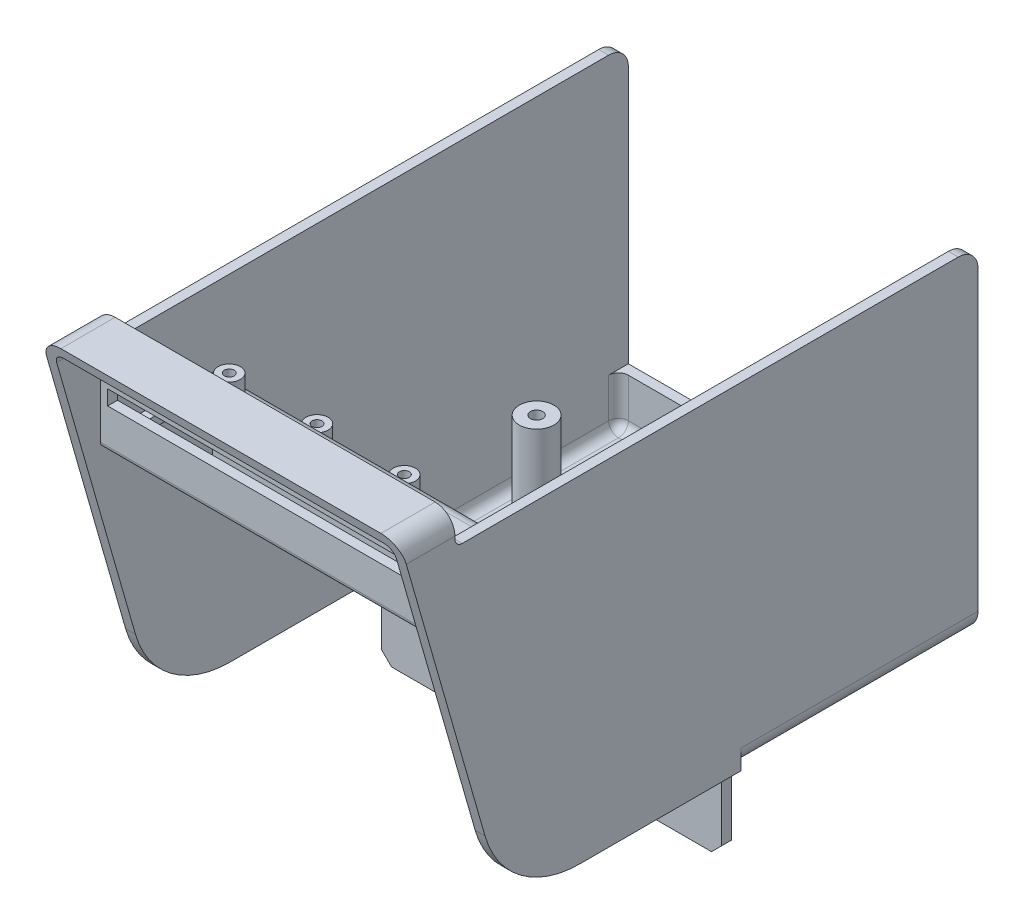
SolidWorks part; units mm, degrees
ref_plane "Front Plane" through (0, 0, 0) normal (0, 0, 1) x (1, 0, 0)
ref_plane "Top Plane" through (0, 0, 0) normal (0, 1, 0) x (1, 0, 0)
ref_plane "Right Plane" through (0, 0, 0) normal (1, 0, 0) x (0, 0, -1)
sketch "Sketch1" plane through (0, 0, 0) normal (0, 1, 0) x (1, 0, 0)
  line L1 (-36.425, -54.49) -> (36.425, -54.49)
  line L2 (-36.425, -54.49) -> (-36.425, 54.49)
  line L3 (-36.425, 54.49) -> (36.425, 54.49)
  line L4 (36.425, -54.49) -> (36.425, 54.49)
  line L5 (-36.425, -54.49) -> (36.425, 54.49) construction
  line L6 (-36.425, 54.49) -> (36.425, -54.49) construction
  point P0 (0, 0)
  dimension "D1" = 72.85
  dimension "D2" = 108.98
extrude "Boss-Extrude1" add sketch "Sketch1" along normal blind 66.66 and the other way blind 7.5
sketch "Sketch2" plane through (36.425, 0, 0) normal (1, 0, 0) x (0, 0, -1)
  line L0 (-54.49, 66.66) -> (-54.49, 43.24)
  line L1 (-54.49, 66.66) -> (-54.49, -7.5) construction
  line L2 (-54.49, 43.24) -> (-31.71, 43.24)
  line L3 (-31.71, 43.24) -> (-31.71, 25.46)
  line L4 (-31.71, 25.46) -> (-14.01, 25.46)
  line L5 (-14.01, 25.46) -> (-14.01, 7.68)
  line L6 (-14.01, 7.68) -> (2.51, 7.68)
  line L7 (2.51, 7.68) -> (2.51, -7.5)
  line L8 (-54.49, -7.5) -> (54.49, -7.5) construction
  line L9 (54.49, 66.66) -> (54.49, -7.5) construction
  line L10 (-54.49, 66.66) -> (54.49, 66.66) construction
  dimension "D1" = 23.42
  dimension "D2" = 86.2
  dimension "D3" = 41.2
  dimension "D4" = 58.98
  dimension "D5" = 68.5
  dimension "D6" = 51.98
extrude "Cut-Extrude1" cut sketch "Sketch2" against normal through all and the other way through all flip side to cut
fillet "Fillet1" radius 1 6 edges at (0, 7.68, -2.51) (0, 25.46, 14.01) (0, 43.24, 31.71) (0, 43.24, 54.49) (0, 25.46, 31.71) (0, 7.68, 14.01)
shell "Shell1" thickness 2 removed face at (0, 29.58, -54.49) removed face at (0, 66.66, 0)
sketch "Sketch3" plane through (0, 43.24, 0) normal (0, -1, 0) x (1, 0, 0)
  line L0 (-36.425, 54.49) -> (36.425, 54.49) construction
  line L1 (-32.5, 47.39) -> (32.5, 47.39)
  line L2 (-32.5, 47.39) -> (-32.5, 37.39)
  line L3 (-32.5, 37.39) -> (32.5, 37.39)
  line L4 (32.5, 47.39) -> (32.5, 37.39)
  line L5 (0, 0) -> (0, 59.3951) construction
  dimension "D1" = 65
  dimension "D2" = 10
  dimension "D3" = 7.1
extrude "Cut-Extrude2" cut sketch "Sketch3" against normal up to next
sketch "Sketch4" plane through (0, 25.46, 0) normal (0, -1, 0) x (1, 0, 0)
  line L0 (-32.5, 47.39) -> (-32.5, 37.39) construction
  line L1 (-32.5, 29.61) -> (32.5, 29.61)
  line L2 (-32.5, 29.61) -> (-32.5, 19.61)
  line L3 (-32.5, 19.61) -> (32.5, 19.61)
  line L4 (32.5, 29.61) -> (32.5, 19.61)
  line L5 (32.5, 37.39) -> (32.5, 47.39) construction
  line L6 (36.425, 31.71) -> (-36.425, 31.71) construction
  dimension "D1" = 2.1
  dimension "D2" = 10
extrude "Cut-Extrude3" cut sketch "Sketch4" against normal up to next
sketch "Sketch5" plane through (0, 7.68, 0) normal (0, -1, 0) x (1, 0, 0)
  line L0 (-32.5, 29.61) -> (-32.5, 19.61) construction
  line L1 (-32.5, 11.91) -> (32.5, 11.91)
  line L2 (-32.5, 11.91) -> (-32.5, 1.91)
  line L3 (-32.5, 1.91) -> (32.5, 1.91)
  line L4 (32.5, 11.91) -> (32.5, 1.91)
  line L5 (32.5, 19.61) -> (32.5, 29.61) construction
  line L6 (36.425, 14.01) -> (-36.425, 14.01) construction
  dimension "D1" = 10
  dimension "D2" = 2.1
extrude "Cut-Extrude4" cut sketch "Sketch5" against normal up to next
sketch "Sketch7" plane through (0, 45.24, 0) normal (0, 1, 0) x (1, 0, 0)
  line L0 (-32.5, -37.39) -> (32.5, -37.39) construction
  circle A0 centre (-28, -34.79) radius 2.25
  circle A1 centre (28, -34.79) radius 2.25
  dimension "D1" = 4.5
  dimension "D4" = 28
  dimension "D5" = 4.5
  dimension "D2" = 28
  dimension "D3" = 2.6
extrude "Boss-Extrude2" add sketch "Sketch7" along normal blind 4.5 and the other way up to next (2 mm away)
sketch "Sketch8" plane through (0, 27.46, 0) normal (0, 1, 0) x (1, 0, 0)
  line L0 (-32.5, -19.61) -> (32.5, -19.61) construction
  circle A0 centre (-28, -17.01) radius 2.25
  circle A1 centre (28, -17.01) radius 2.25
  dimension "D1" = 28
  dimension "D4" = 4.5
  dimension "D2" = 28
  dimension "D3" = 2.6
extrude "Boss-Extrude3" add sketch "Sketch8" along normal blind 4.5 and the other way up to next (2 mm away)
sketch "Sketch9" plane through (0, 9.68, 0) normal (0, 1, 0) x (1, 0, 0)
  line L0 (-32.5, -1.91) -> (32.5, -1.91) construction
  circle A0 centre (-28, 0.69) radius 2.25
  circle A1 centre (28, 0.69) radius 2.25
  dimension "D1" = 4.5
  dimension "D3" = 28
  dimension "D5" = 4.5
  dimension "D2" = 2.6
  dimension "D4" = 28
extrude "Boss-Extrude4" add sketch "Sketch9" along normal blind 4.5 and the other way up to next
sketch "Sketch10" plane through (0, 0, 54.49) normal (0, 0, 1) x (1, 0, 0)
  line L1 (-32.936, 54.3583) -> (33.0803, 54.3583)
  line L2 (-32.936, 54.3583) -> (-32.936, 51.34)
  line L3 (-32.936, 51.34) -> (33.0803, 51.34)
  line L4 (33.0803, 54.3583) -> (33.0803, 51.34)
extrude "Cut-Extrude5" cut sketch "Sketch10" against normal up to next
sketch "Sketch11" plane through (0, -5.5, 0) normal (0, 1, 0) x (1, 0, 0)
  line L0 (34.425, 54.49) -> (-34.425, 54.49) construction
  line L1 (0, 0) -> (0, 57.5418) construction
  circle A0 centre (-25, 24.49) radius 3.5
  circle A1 centre (25, 24.49) radius 3.5
  dimension "D1" = 7
  dimension "D2" = 7
  dimension "D3" = 30
  dimension "D4" = 50
extrude "Boss-Extrude5" add sketch "Sketch11" along normal blind 19.72
sketch "Sketch12" plane through (-36.425, 0, 0) normal (-1, 0, 0) x (0, 0, 1)
  line L0 (54.49, 66.66) -> (64.49, 66.66)
  line L1 (-54.49, -7.5) -> (-2.51, -7.5) construction
  line L2 (64.49, 66.66) -> (47.3791, 6.9873)
  line L4 (-54.49, -7.5) -> (28.1539, -7.5)
  line L5 (-54.49, -7.5) -> (54.49, 66.66)
  arc A1 (47.3791, 6.9873) -> (28.1539, -7.5) centre (28.1539, 12.5) cw
  dimension "D2" = 20
  dimension "D1" = 10
  dimension "D5" = 74
extrude "Boss-Extrude6" add sketch "Sketch12" against normal blind 2
mirror "Mirror1" about plane through (0, 0, 0) normal (1, 0, 0) of "Boss-Extrude6"
sketch "Sketch20" plane through (0, 66.66, 0) normal (0, 1, 0) x (1, 0, 0)
  line L1 (-34.425, -64.49) -> (34.425, -64.49)
  line L2 (-34.425, -64.49) -> (-34.425, -54.49)
  line L3 (-34.425, -54.49) -> (34.425, -54.49)
  line L4 (34.425, -64.49) -> (34.425, -54.49)
extrude "Boss-Extrude7" add sketch "Sketch20" against normal blind 2
sketch "Sketch21" plane through (36.425, 0, 0) normal (1, 0, 0) x (0, 0, -1)
  line L0 (-64.49, 66.66) -> (-63.7125, 63.9486)
  line L1 (-47.3791, 6.9873) -> (-64.49, 66.66) construction
  line L2 (-63.7125, 63.9486) -> (-66.4372, 63.9486)
  line L3 (-66.4372, 63.9486) -> (-64.49, 66.66)
extrude "Cut-Extrude12" cut sketch "Sketch21" against normal through all
chamfer "Chamfer1" [suppressed] distance 4 angle 15
fillet "Fillet3" [suppressed] radius 1
sketch "Sketch13" plane through (0, -7.5, 0) normal (0, -1, 0) x (1, 0, 0)
  line L1 (-34.425, -54.49) -> (34.425, -54.49)
  line L2 (-34.425, -54.49) -> (-34.425, -51.99)
  line L3 (-34.425, -51.99) -> (34.425, -51.99)
  line L4 (34.425, -54.49) -> (34.425, -51.99)
  dimension "D1" = 2.5
extrude "Cut-Extrude6" cut sketch "Sketch13" against normal up to next
fillet "Fillet4" radius 3 2 edges at (-35.425, 66.66, -54.49) (35.425, 66.66, -54.49)
sketch "Sketch14" plane through (0, 66.66, 0) normal (0, 1, 0) x (1, 0, 0)
  line L11 (-35.425, 64.9406) -> (35.425, 64.9406)
  line L15 (-35.425, -32.71) -> (-35.425, -53.49)
  line L17 (-35.425, -53.49) -> (35.425, -53.49)
  line L18 (35.425, -53.49) -> (35.425, 51.49)
  line L19 (-35.425, 64.9406) -> (-35.425, -53.49)
  line L20 (-35.425, -53.49) -> (35.425, -53.49)
  line L21 (35.425, -53.49) -> (35.425, 64.9406)
  dimension "D1" = 1
extrude "Cut-Extrude7" cut sketch "Sketch14" against normal blind 1.5
sketch "Sketch16" plane through (0, -7.5, 0) normal (0, -1, 0) x (1, 0, 0)
  line L0 (34.425, -51.99) -> (-34.425, -51.99) construction
  circle A0 centre (-25, -24.49) radius 1.25
  circle A1 centre (25, -24.49) radius 1.25
  dimension "D1" = 2.5
  dimension "D2" = 2.5
  dimension "D3" = 27.5
  dimension "D4" = 27.5
extrude "Cut-Extrude8" cut sketch "Sketch16" against normal up to next
sketch "Sketch17" plane through (0, 14.18, 0) normal (0, 1, 0) x (1, 0, 0)
  circle A0 centre (-28, 0.69) radius 1
  circle A1 centre (28, 0.69) radius 1
  dimension "D1" = 2
  dimension "D2" = 2
extrude "Cut-Extrude9" cut sketch "Sketch17" against normal blind 4
sketch "Sketch18" plane through (0, 31.96, 0) normal (0, 1, 0) x (1, 0, 0)
  circle A0 centre (-28, -17.01) radius 1
  circle A1 centre (28, -17.01) radius 1
  dimension "D1" = 2
  dimension "D2" = 2
extrude "Cut-Extrude10" cut sketch "Sketch18" against normal blind 4
sketch "Sketch19" plane through (0, 49.74, 0) normal (0, 1, 0) x (1, 0, 0)
  circle A0 centre (-28, -34.79) radius 1
  circle A1 centre (28, -34.79) radius 1
  dimension "D1" = 2
  dimension "D2" = 2
extrude "Cut-Extrude11" cut sketch "Sketch19" against normal blind 4
sketch "Sketch22" plane through (36.425, 0, 0) normal (1, 0, 0) x (0, 0, -1)
  line L0 (54.49, 63.66) -> (54.49, -7.5) construction
  line L1 (54.49, 60.66) -> (-53.49, 60.66)
  line L2 (54.49, 60.66) -> (54.49, 66.66)
  line L3 (54.49, 66.66) -> (-53.49, 66.66)
  line L4 (-53.49, 60.66) -> (-53.49, 66.66)
  line L5 (48.51, 60.66) -> (-51.99, 60.66) construction
extrude "Cut-Extrude13" cut sketch "Sketch22" against normal through all
sketch "Sketch23" plane through (0, 60.66, 0) normal (0, 1, 0) x (1, 0, 0)
  line L1 (-34.425, -52.49) -> (34.425, -52.49)
  line L2 (-34.425, -52.49) -> (-34.425, -53.49)
  line L3 (-34.425, -53.49) -> (34.425, -53.49)
  line L4 (34.425, -52.49) -> (34.425, -53.49)
  line L5 (34.425, -52.49) -> (34.425, -32.71) construction
  line L6 (-36.425, -53.49) -> (36.425, -53.49) construction
extrude "Boss-Extrude8" add sketch "Sketch23" along normal offset from surface (4 mm away) 2 up to face at (0, 66.66, 58.99)
fillet "Fillet6" radius 2 2 edges at (-34.425, 64.66, 52.99) (34.425, 64.66, 52.99)
fillet "Fillet7" radius 2 2 edges at (34.425, 64.66, 59.2033) (-34.425, 64.66, 59.2033)
fillet "Fillet8" radius 4 2 edges at (36.425, 66.66, 58.99) (-36.425, 66.66, 58.99)
sketch "Sketch28" plane through (0, -7.5, 0) normal (0, -1, 0) x (1, 0, 0)
  line L0 (34.425, -2.51) -> (34.425, 28.1539) construction
  line L1 (-34.425, -2.51) -> (34.425, -2.51)
  line L2 (-34.425, -2.51) -> (-34.425, -4.51)
  line L3 (-34.425, -4.51) -> (34.425, -4.51)
  line L4 (34.425, -2.51) -> (34.425, -4.51)
  dimension "D1" = 2
extrude "Boss-Extrude10" add sketch "Sketch28" along normal blind 15.2
chamfer "Chamfer2" distance 2 angle 45 2 edges at (-34.425, -22.7, -3.51) (34.425, -22.7, -3.51)
sketch "Sketch29" plane through (0, 0, -2.51) normal (0, 0, 1) x (1, 0, 0)
  line L0 (-24.425, -14.7) -> (24.425, -14.7) construction
  line L1 (0, 0) -> (0, -14.7) construction
  line L2 (32.425, -22.7) -> (-32.425, -22.7) construction
  circle A0 centre (-24.425, -14.7) radius 1.75
  circle A1 centre (24.425, -14.7) radius 1.75
  dimension "D3" = 3.5
  dimension "D1" = 8
  dimension "D2" = 48.85
extrude "Cut-Extrude16" cut sketch "Sketch29" against normal through all
fillet "Fillet10" radius 2 2 edges at (-34.425, -5.5, -28.25) (34.425, -5.5, -28.25)
sketch "Sketch30" plane through (0, 0, -54.49) normal (0, 0, -1) x (-1, 0, 0)
  line L0 (-36.425, -3.5) -> (-36.425, -7.5)
  line L1 (-36.425, -7.5) -> (-32.425, -7.5)
  line L2 (0, -7.5) -> (0, 0) construction
  line L3 (34.425, -7.5) -> (-34.425, -7.5) construction
  line L4 (36.425, -7.5) -> (32.425, -7.5)
  line L5 (36.425, -3.5) -> (36.425, -7.5)
  arc A1 (-36.425, -3.5) -> (-32.425, -7.5) centre (-32.425, -3.5) ccw
  arc A2 (-34.425, -3.5) -> (-32.425, -5.5) centre (-32.425, -3.5) ccw construction
  arc A3 (36.425, -3.5) -> (32.425, -7.5) centre (32.425, -3.5) cw
  dimension "D1" = 8
extrude "Cut-Extrude17" cut sketch "Sketch30" against normal up to surface (49.98 mm away) up to face at (26.175, -14.7, -4.51)
sketch "Sketch31" plane through (0, 0, 0) normal (-1, 0, 0) x (0, 0, 1)
  line L0 (-4.51, -7.5) -> (-51.99, -7.5) construction
  line L1 (-54.49, 60.66) -> (-51.99, 60.66)
  line L2 (-54.49, 60.66) -> (-54.49, -7.5)
  line L3 (-54.49, -7.5) -> (-51.99, -7.5)
  line L4 (-51.99, 60.66) -> (-51.99, -7.5)
  line L5 (-51.99, -3.5) -> (-51.99, -6.9641) construction
extrude "Cut-Extrude18" cut sketch "Sketch31" against normal mid plane 179.66
sketch "Sketch32" plane through (0, 0, -51.99) normal (0, 0, -1) x (-1, 0, 0)
  line L8 (-34.425, -3.5) -> (-34.425, 60.66)
  line L9 (-34.425, 60.66) -> (-36.425, 60.66)
  line L10 (-36.425, 60.66) -> (-36.425, -3.5)
  line L11 (-32.425, -7.5) -> (32.425, -7.5)
  line L12 (36.425, -3.5) -> (36.425, 60.66)
  line L13 (36.425, 60.66) -> (34.425, 60.66)
  line L14 (34.425, 60.66) -> (34.425, -3.5)
  line L15 (32.425, -5.5) -> (-32.425, -5.5)
  line L16 (-34.425, -3.5) -> (-34.425, 60.66)
  line L17 (-34.425, 60.66) -> (-36.425, 60.66)
  line L18 (-36.425, 60.66) -> (-36.425, -3.5)
  line L19 (-32.425, -7.5) -> (32.425, -7.5)
  line L20 (36.425, -3.5) -> (36.425, 60.66)
  line L21 (36.425, 60.66) -> (34.425, 60.66)
  line L22 (34.425, 60.66) -> (34.425, -3.5)
  line L23 (32.425, -5.5) -> (-32.425, -5.5)
  arc A3 (-34.425, -3.5) -> (-32.425, -5.5) centre (-32.425, -3.5) ccw
  arc A4 (-36.425, -3.5) -> (-32.425, -7.5) centre (-32.425, -3.5) ccw
  arc A5 (32.425, -5.5) -> (34.425, -3.5) centre (32.425, -3.5) ccw
  arc A6 (-34.425, -3.5) -> (-32.425, -5.5) centre (-32.425, -3.5) ccw
  arc A7 (-36.425, -3.5) -> (-32.425, -7.5) centre (-32.425, -3.5) ccw
  arc A8 (32.425, -5.5) -> (34.425, -3.5) centre (32.425, -3.5) ccw
  arc A10 (32.425, -7.5) -> (36.425, -3.5) centre (32.425, -3.5) ccw
  arc A11 (32.425, -7.5) -> (36.425, -3.5) centre (32.425, -3.5) ccw
  dimension "D1" = 0
extrude "Boss-Extrude11" add sketch "Sketch32" along normal blind 0.52
sketch "Sketch33" plane through (0, -5.5, 0) normal (0, 1, 0) x (1, 0, 0)
  line L0 (34.425, 52.51) -> (34.425, 4.51) construction
  line L1 (-34.425, 52.51) -> (34.425, 52.51)
  line L2 (-34.425, 52.51) -> (-34.425, 50.51)
  line L3 (-34.425, 50.51) -> (34.425, 50.51)
  line L4 (34.425, 52.51) -> (34.425, 50.51)
  dimension "D1" = 2
extrude "Boss-Extrude12" add sketch "Sketch33" along normal blind 10
fillet "Fillet11" radius 2 5 edges at (-34.425, 0.5, -50.51) (-33.8392, -4.9142, -50.51) (34.425, 0.5, -50.51) (33.8392, -4.9142, -50.51) (0, -5.5, -50.51)
fillet "Fillet12" radius 4 2 edges at (35.425, 60.66, -52.51) (-35.425, 60.66, -52.51)
fillet "Fillet13" radius 1.5 2 edges at (35.425, 60.66, 53.49) (-35.425, 60.66, 53.49)
